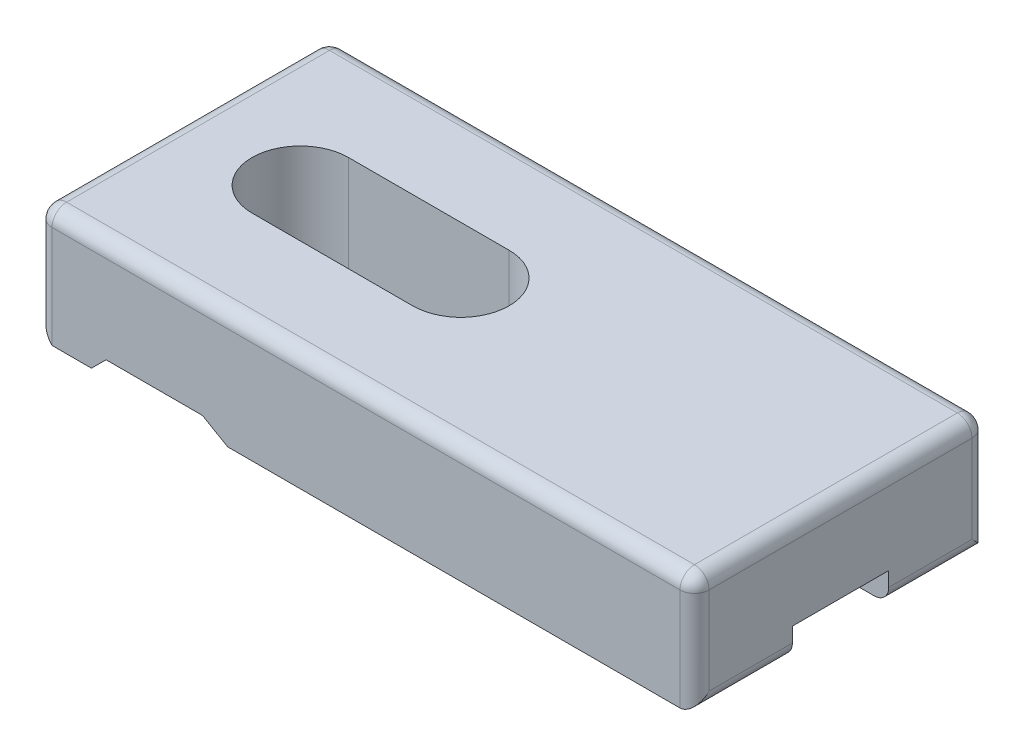
SolidWorks part; units mm, degrees
material "AISI 1045 钢，冷拔"
ref_plane "前视基准面" through (0, 0, 0) normal (0, 0, 1) x (1, 0, 0)
ref_plane "上视基准面" through (0, 0, 0) normal (0, 1, 0) x (1, 0, 0)
ref_plane "右视基准面" through (0, 0, 0) normal (1, 0, 0) x (0, 0, -1)
sketch "草图1" plane through (0, 0, 0) normal (0, 1, 0) x (1, 0, 0)
  line L0 (19, 10) -> (8, 10) construction
  line L1 (0, 0) -> (45, 0)
  line L2 (0, 0) -> (0, 20)
  line L3 (0, 20) -> (45, 20)
  line L4 (45, 0) -> (45, 20)
  line L5 (19, 6.7) -> (8, 6.7)
  line L6 (19, 13.3) -> (8, 13.3)
  arc A0 (19, 6.7) -> (19, 13.3) centre (19, 10) ccw
  arc A1 (8, 13.3) -> (8, 6.7) centre (8, 10) ccw
  point P7 (13.5, 10)
  dimension "D5" = 3.3
  dimension "D1" = 45
  dimension "D2" = 20
  dimension "D3" = 19
  dimension "D4" = 11
  dimension "D6" = 10
extrude "凸台-拉伸1" add sketch "草图1" along normal blind 8
sketch "草图2" plane through (0, 0, 0) normal (0, -1, 0) x (1, 0, 0)
  line L2 (45, 0) -> (45, -20) construction
  line L3 (45, -6.7) -> (45, -13.3)
  line L4 (45, -13.3) -> (8, -13.3)
  line L13 (8, -6.7) -> (45, -6.7)
  arc A0 (8, -6.7) -> (8, -13.3) centre (8, -10) ccw
  dimension "D1" = 3.3
extrude "切除-拉伸1" cut sketch "草图2" against normal blind 2
sketch "草图3" plane through (0, 0, 0) normal (0, -1, 0) x (1, 0, 0)
  line L0 (0, -6.7) -> (4.7, -6.7)
  line L1 (0, -20) -> (0, 0) construction
  line L3 (0, -13.3) -> (4.7, -13.3)
  line L4 (4.7, 0) -> (4.7, -6.7)
  line L5 (0, 0) -> (45, 0) construction
  line L6 (45, -20) -> (0, -20) construction
  line L7 (11.3, 0) -> (11.3, -20)
  line L8 (4.7, -13.3) -> (4.7, -20)
  line L9 (4.7, 0) -> (11.3, 0)
  line L10 (4.7, -20) -> (11.3, -20)
  line L11 (0, -6.7) -> (0, -13.3)
  dimension "D1" = 6.6
  dimension "D2" = 6.6
  dimension "D3" = 6.7
  dimension "D4" = 4.7
extrude "切除-拉伸2" cut sketch "草图3" against normal blind 1
chamfer "倒角1" distance 1 angle 45 4 edges at (0, 0, -16.65) (4.7, 0, -16.65) (4.7, 0, -3.35) (0, 0, -3.35)
chamfer "倒角2" distance 1 angle 60 2 edges at (11.3, 0, -16.65) (11.3, 0, -3.35) first distance on face at (11.3, 0.5, -16.65) first distance on face at (11.3, 0.5, -3.35)
fillet "圆角1" radius 1 10 edges at (22.5, 8, -20) (45, 8, -10) (22.5, 8, 0) (0, 8, -10) (45, 4, 0) (45, 4, -20) (0, 4.5, -20) (0, 4.5, 0) (45, 0, -16.65) (45, 0, -3.35)
